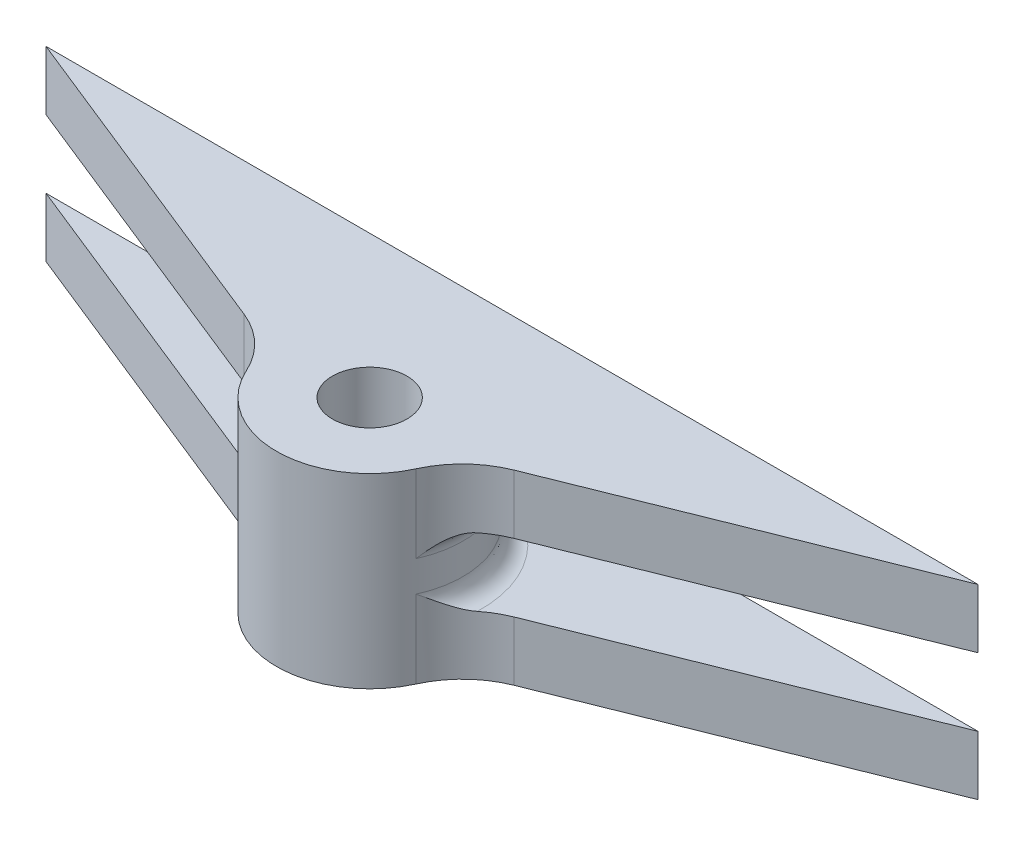
SolidWorks part; units mm, degrees
ref_plane "Front Plane" through (0, 0, 0) normal (0, 0, 1) x (1, 0, 0)
ref_plane "Top Plane" through (0, 0, 0) normal (0, 1, 0) x (1, 0, 0)
ref_plane "Right Plane" through (0, 0, 0) normal (1, 0, 0) x (0, 0, -1)
sketch "Sketch1" plane through (0, 0, 0) normal (0, 1, 0) x (1, 0, 0)
  line L0 (0, 0) -> (100, 0)
  line L4 (0, 0) -> (40.0326, -16.076)
  line L5 (59.9674, -16.076) -> (100, 0)
  line L6 (50, 0) -> (50, -17.1488) construction
  line L7 (40.0326, -16.076) -> (59.9674, -16.076) construction
  circle A0 centre (50, -15.2697) radius 4
  circle A1 centre (50, -15.2697) radius 10
  dimension "D2" = 20
  dimension "D3" = 8
  dimension "D1" = 100
extrude "Boss-Extrude1" add sketch "Sketch1" along normal blind 6.35 contours A1 L5 L0 L4 region at (50, 0, 5.1088)
extrude "Boss-Extrude2" add sketch "Sketch1<3>" along normal blind 20 contours A1 A0 region at (49.6079, 0, 5.5605)
sketch "Sketch1<3>" plane through (0, 0, 0) normal (0, 1, 0) x (1, 0, 0) same geometry as "Sketch1"
ref_plane "Plane1" through (0, 10, 0) normal (0, 1, 0) x (1, 0, 0)
mirror "Mirror1" about plane through (0, 10, 0) normal (0, 1, 0) of "Boss-Extrude1"
ref_plane "Plane2" through (59.9674, 13.65, 16.076) normal (0, 1, 0) x (1, 0, 0)
fillet "Fillet1" radius 10 4 edges at (59.9674, 3.175, 16.076) (40.0326, 3.175, 16.076) (40.0326, 16.825, 16.076) (59.9674, 16.825, 16.076)
fillet "Fillet2" radius 2 2 edges at (50, 6.35, 5.2697) (50, 13.65, 5.2697)
